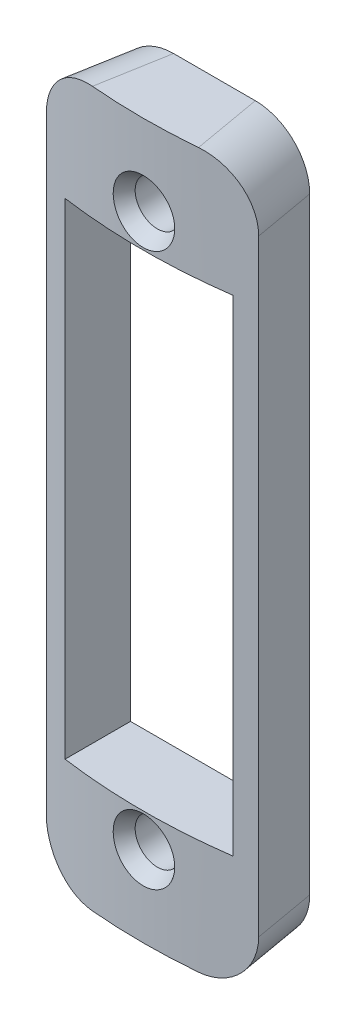
SolidWorks part; units mm, degrees
material "ABS"
ref_plane "Front Plane" through (0, 0, 0) normal (0, 0, 1) x (1, 0, 0)
ref_plane "Top Plane" through (0, 0, 0) normal (0, 1, 0) x (1, 0, 0)
ref_plane "Right Plane" through (0, 0, 0) normal (1, 0, 0) x (0, 0, -1)
sketch "Sketch1" plane through (0, 0, 0) normal (1, 0, 0) x (0, 0, -1)
  line L0 (34.25, 0) -> (34.25, 16.293) construction
  line L2 (0, 0) -> (2, 0)
  line L3 (0, 0) -> (0, 40)
  line L4 (0, 40) -> (2, 40)
  line L5 (2, 0) -> (2, 40)
  dimension "D1" = 34.25
  dimension "D2" = 2
  dimension "D3" = 40
revolve "BULK EXTRUDE" add sketch "Sketch1" angle 20 mid plane about L0
sketch "Sketch2" plane through (0, 0, 0) normal (0, 0, 1) x (1, 0, 0)
  line L0 (0, 0) -> (0, 6.4) construction
  line L1 (-4.7, 33.6) -> (4.7, 33.6)
  line L2 (-4.7, 33.6) -> (-4.7, 6.4)
  line L3 (-4.7, 6.4) -> (4.7, 6.4)
  line L4 (4.7, 33.6) -> (4.7, 6.4)
  line L5 (0, 33.6) -> (0, 35.48) construction
  line L6 (0, 6.4) -> (0, 4.52) construction
  circle A0 centre (0, 4.52) radius 1.25
  circle A1 centre (0, 35.48) radius 1.25
  point P7 (-4.7, 20)
  dimension "D4" = 2.5
  dimension "D1" = 27.2
  dimension "D2" = 9.4
  dimension "D3" = 20
  dimension "D5" = 30.96
extrude "CONNECTOR PASSTHRU" cut sketch "Sketch2" against normal through all both and the other way through all
ref_plane "REAR FLATTENING PLANE" through (0, 0, -2.4899) normal (0, 0, 1) x (1, 0, 0)
sketch "Sketch3" plane through (0, 0, -2.4899) normal (0, 0, 1) x (1, 0, 0)
  line L0 (4.7, 6.4) -> (4.7, 33.6) construction
  line L1 (4.7, 6.4) -> (-4.7, 6.4) construction
  line L2 (-4.7, 33.6) -> (-4.7, 6.4) construction
  line L3 (-4.7, 33.6) -> (4.7, 33.6) construction
  line L4 (-5.6002, 0) -> (5.6002, 0)
  line L5 (-5.6002, 40) -> (-5.6002, 0)
  line L6 (5.6002, 40) -> (-5.6002, 40)
  line L7 (5.6002, 0) -> (5.6002, 40)
  line L8 (-5.6002, 0) -> (5.6002, 0)
  line L9 (-5.6002, 40) -> (-5.6002, 0)
  line L10 (5.6002, 40) -> (-5.6002, 40)
  line L11 (5.6002, 0) -> (5.6002, 40)
  line L12 (4.7, 6.4) -> (4.7, 33.6)
  line L13 (4.7, 6.4) -> (-4.7, 6.4)
  line L14 (-4.7, 33.6) -> (-4.7, 6.4)
  line L15 (-4.7, 33.6) -> (4.7, 33.6)
  circle A0 centre (0, 4.52) radius 1.25 construction
  circle A1 centre (0, 35.48) radius 1.25 construction
  circle A2 centre (0, 4.52) radius 1.25
  circle A3 centre (0, 35.48) radius 1.25
  dimension "D1" = 0
extrude "REAR FLATTENING" add sketch "Sketch3" along normal up to next and the other way blind 1.5
sketch "Sketch4" plane through (5.8571, 0, -1.0328) normal (0.9848, 0, -0.1736) x (-0.1736, 0, -0.9848)
  line L1 (-0.5203, 40) -> (4.9018, 40)
  line L2 (-0.5203, 40) -> (-0.5203, 0)
  line L3 (-0.5203, 0) -> (4.9018, 0)
  line L4 (4.9018, 40) -> (4.9018, 0)
extrude "Cut-Extrude2" cut sketch "Sketch4" along normal through all
sketch "Sketch5" plane through (-5.8571, 0, -1.0328) normal (-0.9848, 0, -0.1736) x (-0.1736, 0, 0.9848)
  line L1 (0.5203, 40) -> (-4.8559, 40)
  line L2 (0.5203, 40) -> (0.5203, 0)
  line L3 (0.5203, 0) -> (-4.8559, 0)
  line L4 (-4.8559, 40) -> (-4.8559, 0)
extrude "Cut-Extrude3" cut sketch "Sketch5" along normal through all
fillet "Fillet1" radius 3 4 edges at (5.6416, 40, -2.2551) (5.6416, 0, -2.2551) (-5.6416, 0, -2.2551) (-5.6416, 40, -2.2551)
ref_axis "Axis1" through (0, 4.52, -3.9899) along (0, 0, 1)
ref_plane "Plane1" through (0, 0, 0) normal (-1, 0, 0) x (0, 0, 1)
sketch "Sketch6" plane through (0, 0, 0) normal (-1, 0, 0) x (0, 0, 1)
  line L0 (0, 4.52) -> (0, 6.27)
  line L1 (-3.9899, 4.52) -> (0, 4.52) construction
  line L2 (0, 6.27) -> (-1, 5.645)
  line L3 (-1, 5.645) -> (-1, 4.52)
  line L4 (-1, 4.52) -> (0, 4.52)
  dimension "D1" = 1
  dimension "D2" = 1.75
  dimension "D3" = 1.125
revolve "Cut-Revolve1" cut sketch "Sketch6" angle 360 about axis through (0, 4.52, -3.9899) along (0, 0, 1)
ref_plane "Plane2" through (0, 20, 0) normal (0, 1, 0) x (1, 0, 0)
mirror "Mirror1" about plane through (0, 20, 0) normal (0, 1, 0) of "Cut-Revolve1"
